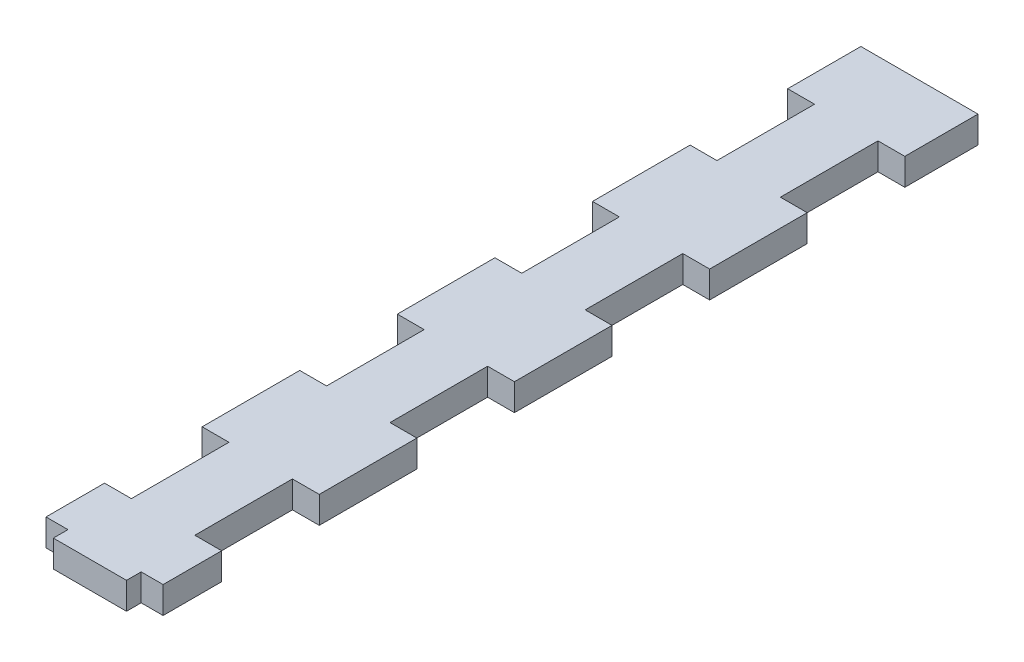
SolidWorks part; units mm, degrees
ref_plane "Alzado" through (0, 0, 0) normal (0, 0, 1) x (1, 0, 0)
ref_plane "Planta" through (0, 0, 0) normal (0, 1, 0) x (1, 0, 0)
ref_plane "Vista lateral" through (0, 0, 0) normal (1, 0, 0) x (0, 0, -1)
sketch "Croquis1" plane through (0, 0, 0) normal (0, 1, 0) x (1, 0, 0)
  line L0 (4.5, 0) -> (19.5, 0)
  line L1 (24, 3) -> (24, 15)
  line L2 (24, 170) -> (0, 170)
  line L3 (0, 170) -> (0, 155)
  line L4 (12, 0) -> (19.5, 0)
  line L5 (0, 85) -> (0, 95)
  line L6 (0, 95) -> (5.5, 95)
  line L7 (5.5, 95) -> (5.5, 115)
  line L8 (5.5, 115) -> (0, 115)
  line L9 (0, 115) -> (0, 135)
  line L10 (0, 135) -> (5.5, 135)
  line L11 (5.5, 135) -> (5.5, 155)
  line L12 (5.5, 155) -> (0, 155)
  line L13 (5.5, 15) -> (0, 15)
  line L14 (5.5, 35) -> (5.5, 15)
  line L15 (0, 35) -> (5.5, 35)
  line L16 (5.5, 55) -> (0, 55)
  line L17 (5.5, 75) -> (5.5, 55)
  line L18 (0, 75) -> (5.5, 75)
  line L19 (24, 75) -> (18.5, 75)
  line L20 (18.5, 75) -> (18.5, 55)
  line L21 (18.5, 55) -> (24, 55)
  line L22 (24, 35) -> (18.5, 35)
  line L23 (18.5, 35) -> (18.5, 15)
  line L24 (18.5, 15) -> (24, 15)
  line L25 (18.5, 155) -> (24, 155)
  line L26 (18.5, 135) -> (18.5, 155)
  line L27 (24, 135) -> (18.5, 135)
  line L28 (18.5, 115) -> (24, 115)
  line L29 (18.5, 95) -> (18.5, 115)
  line L30 (24, 95) -> (18.5, 95)
  line L31 (19.5, 0) -> (19.5, 3)
  line L32 (19.5, 3) -> (24, 3)
  line L33 (12, 0) -> (4.5, 0)
  line L34 (4.5, 0) -> (4.5, 3)
  line L35 (4.5, 3) -> (0, 3)
  line L36 (0, 15) -> (0, 3)
  line L37 (0, 55) -> (0, 35)
  line L38 (0, 95) -> (0, 75)
  line L39 (0, 135) -> (0, 115)
  line L40 (24, 155) -> (24, 170)
  line L41 (24, 115) -> (24, 135)
  line L42 (24, 75) -> (24, 95)
  line L43 (24, 35) -> (24, 55)
  dimension "D1" = 20
  dimension "D2" = 20
  dimension "D3" = 7.5
  dimension "D4" = 10
  dimension "D5" = 20
  dimension "D6" = 20
  dimension "D7" = 20
  dimension "D8" = 3
  dimension "D9" = 20
  dimension "D10" = 12
  dimension "D11" = 3
  dimension "D12" = 15
  dimension "D13" = 15
  dimension "D14" = 12
  dimension "D15" = 20
  dimension "D16" = 20
extrude "Saliente-Extruir1" add sketch "Croquis1" along normal blind 5.5 contours L22 L43 L21 L20 L19 L42 L30 L29 L28 L41 L27 L26 L25 L40 L2 L3 L12 L11 L10 L9 L8 L7 L6 L5 L38 L18 L17 L16 L37 L15 L14 L13 L36 L35 L34 L0 L31 L32 L1 L24 L23 region at (12, 0, -85.7105)
